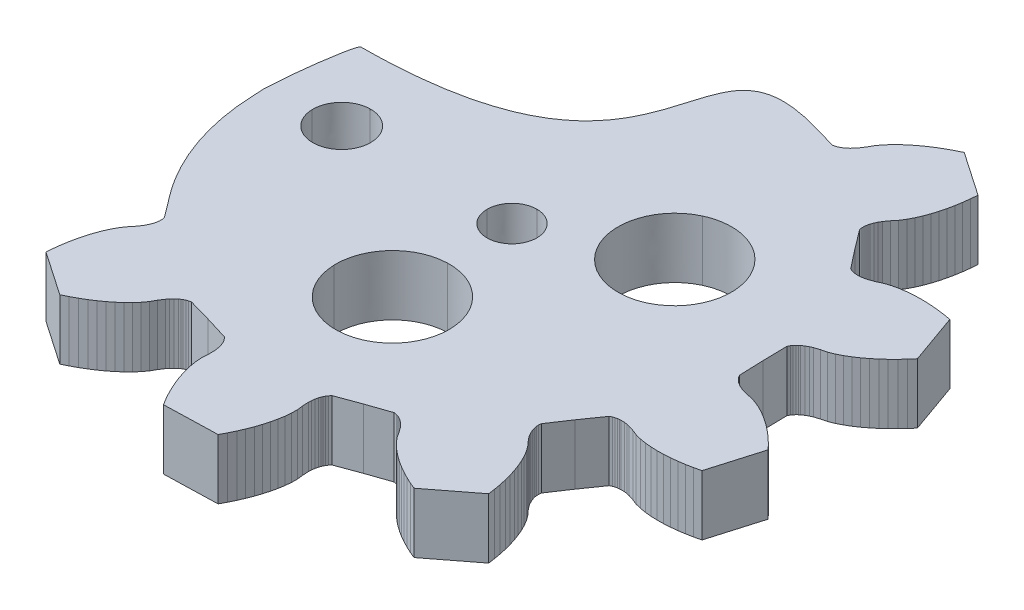
SolidWorks part; units mm, degrees
material "Acrylic (Medium-high impact)"
ref_plane "Front Plane" through (0, 0, 0) normal (0, 0, 1) x (1, 0, 0)
ref_plane "Top Plane" through (0, 0, 0) normal (0, 1, 0) x (1, 0, 0)
ref_plane "Right Plane" through (0, 0, 0) normal (1, 0, 0) x (0, 0, -1)
sketch "Sketch1" plane through (0, 0, 0) normal (0, 1, 0) x (1, 0, 0)
  line L0 (10.7037, 1.5046) -> (10.6812, 2.7875)
  line L1 (10.6812, 2.7875) -> (10.7422, 2.9087)
  line L2 (10.7422, 2.9087) -> (10.8065, 2.9999)
  line L3 (10.8065, 2.9999) -> (10.873, 3.0751)
  line L4 (10.873, 3.0751) -> (10.9407, 3.1393)
  line L5 (10.9407, 3.1393) -> (11.0092, 3.1955)
  line L6 (11.0092, 3.1955) -> (11.1488, 3.2908)
  line L7 (11.1488, 3.2908) -> (11.291, 3.3685)
  line L8 (11.291, 3.3685) -> (11.4351, 3.4325)
  line L9 (11.4351, 3.4325) -> (11.7287, 3.5294)
  line L10 (11.7287, 3.5294) -> (12.0254, 3.6057)
  line L11 (12.0254, 3.6057) -> (12.3155, 3.7204)
  line L12 (12.3155, 3.7204) -> (12.6002, 3.8632)
  line L13 (12.6002, 3.8632) -> (12.8799, 4.0289)
  line L14 (12.8799, 4.0289) -> (13.155, 4.2143)
  line L15 (13.155, 4.2143) -> (13.4253, 4.4178)
  line L16 (13.4253, 4.4178) -> (13.6904, 4.6381)
  line L17 (13.6904, 4.6381) -> (13.9504, 4.8747)
  line L18 (13.9504, 4.8747) -> (14.2047, 5.1263)
  line L19 (14.2047, 5.1263) -> (14.4534, 5.393)
  line L20 (14.4534, 5.393) -> (14.6958, 5.674)
  line L21 (14.6958, 5.674) -> (13.7536, 8.3269)
  line L22 (13.7536, 8.3269) -> (13.3887, 8.3913)
  line L23 (13.3887, 8.3913) -> (13.0276, 8.4407)
  line L24 (13.0276, 8.4407) -> (12.6717, 8.4749)
  line L25 (12.6717, 8.4749) -> (12.3211, 8.4938)
  line L26 (12.3211, 8.4938) -> (11.9764, 8.4967)
  line L27 (11.9764, 8.4967) -> (11.6387, 8.4833)
  line L28 (11.6387, 8.4833) -> (11.3085, 8.453)
  line L29 (11.3085, 8.453) -> (10.9871, 8.4044)
  line L30 (10.9871, 8.4044) -> (10.6763, 8.3351)
  line L31 (10.6763, 8.3351) -> (10.3793, 8.2405)
  line L32 (10.3793, 8.2405) -> (10.101, 8.1117)
  line L33 (10.101, 8.1117) -> (9.8124, 8.0012)
  line L34 (9.8124, 8.0012) -> (9.6601, 7.9597)
  line L35 (9.6601, 7.9597) -> (9.5011, 7.9299)
  line L36 (9.5011, 7.9299) -> (9.3329, 7.9154)
  line L37 (9.3329, 7.9154) -> (9.2442, 7.9156)
  line L38 (9.2442, 7.9156) -> (9.1513, 7.9227)
  line L39 (9.1513, 7.9227) -> (9.0525, 7.939)
  line L40 (9.0525, 7.939) -> (8.945, 7.9688)
  line L41 (8.945, 7.9688) -> (8.8213, 8.0241)
  line L42 (8.8213, 8.0241) -> (8.0297, 9.0328)
  line L43 (8.0297, 9.0328) -> (7.2586, 10.0578)
  line L44 (7.2586, 10.0578) -> (7.237, 10.192)
  line L45 (7.237, 10.192) -> (7.2356, 10.3036)
  line L46 (7.2356, 10.3036) -> (7.2453, 10.4034)
  line L47 (7.2453, 10.4034) -> (7.2622, 10.495)
  line L48 (7.2622, 10.495) -> (7.2848, 10.5812)
  line L49 (7.2848, 10.5812) -> (7.3417, 10.7403)
  line L50 (7.3417, 10.7403) -> (7.4112, 10.8869)
  line L51 (7.4112, 10.8869) -> (7.4902, 11.0235)
  line L52 (7.4902, 11.0235) -> (7.671, 11.2748)
  line L53 (7.671, 11.2748) -> (7.8661, 11.5114)
  line L54 (7.8661, 11.5114) -> (8.0336, 11.775)
  line L55 (8.0336, 11.775) -> (8.18, 12.0582)
  line L56 (8.18, 12.0582) -> (8.3091, 12.3569)
  line L57 (8.3091, 12.3569) -> (8.4229, 12.6689)
  line L58 (8.4229, 12.6689) -> (8.5221, 12.9925)
  line L59 (8.5221, 12.9925) -> (8.6074, 13.3271)
  line L60 (8.6074, 13.3271) -> (8.6791, 13.6714)
  line L61 (8.6791, 13.6714) -> (8.7371, 14.0249)
  line L62 (8.7371, 14.0249) -> (8.7818, 14.387)
  line L63 (8.7818, 14.387) -> (8.813, 14.7572)
  line L64 (8.813, 14.7572) -> (6.4943, 16.3485)
  line L65 (6.4943, 16.3485) -> (6.1611, 16.1857)
  line L66 (6.1611, 16.1857) -> (5.8402, 16.013)
  line L67 (5.8402, 16.013) -> (5.5321, 15.8312)
  line L68 (5.5321, 15.8312) -> (5.2374, 15.6398)
  line L69 (5.2374, 15.6398) -> (4.957, 15.4395)
  line L70 (4.957, 15.4395) -> (4.6913, 15.2298)
  line L71 (4.6913, 15.2298) -> (4.4421, 15.0108)
  line L72 (4.4421, 15.0108) -> (4.2108, 14.7822)
  line L73 (4.2108, 14.7822) -> (4, 14.5431)
  line L74 (4, 14.5431) -> (3.8149, 14.2916)
  line L75 (3.8149, 14.2916) -> (3.6655, 14.0236)
  line L76 (3.6655, 14.0236) -> (3.4969, 13.7644)
  line L77 (3.4969, 13.7644) -> (3.3982, 13.641)
  line L78 (3.3982, 13.641) -> (3.287, 13.5232)
  line L79 (3.287, 13.5232) -> (3.1591, 13.4124)
  line L80 (3.1591, 13.4124) -> (3.0873, 13.3603)
  line L81 (3.0873, 13.3603) -> (3.0081, 13.3113)
  line L82 (3.0081, 13.3113) -> (2.9187, 13.2664)
  line L83 (2.9187, 13.2664) -> (2.8143, 13.2271)
  line L84 (2.8143, 13.2271) -> (2.6818, 13.199)
  line L85 (2.6818, 13.199) -> (1.4492, 13.5492)
  line L86 (-14.9201, 0.7879) -> (-14.8842, 0.1165)
  line L87 (-12.425, -6.74) -> (-11.6539, -7.7649)
  line L88 (-11.6539, -7.7649) -> (-11.6324, -7.8989)
  line L89 (-11.6324, -7.8989) -> (-11.6311, -8.0107)
  line L90 (-11.6311, -8.0107) -> (-11.6405, -8.1103)
  line L91 (-11.6405, -8.1103) -> (-11.6577, -8.2021)
  line L92 (-11.6577, -8.2021) -> (-11.6802, -8.2883)
  line L93 (-11.6802, -8.2883) -> (-11.737, -8.4474)
  line L94 (-11.737, -8.4474) -> (-11.8067, -8.594)
  line L95 (-11.8067, -8.594) -> (-11.8857, -8.7307)
  line L96 (-11.8857, -8.7307) -> (-12.0661, -8.9818)
  line L97 (-12.0661, -8.9818) -> (-12.2615, -9.2185)
  line L98 (-12.2615, -9.2185) -> (-12.4288, -9.4819)
  line L99 (-12.4288, -9.4819) -> (-12.5752, -9.7653)
  line L100 (-12.5752, -9.7653) -> (-12.7045, -10.0639)
  line L101 (-12.7045, -10.0639) -> (-12.8182, -10.3758)
  line L102 (-12.8182, -10.3758) -> (-12.9174, -10.6997)
  line L103 (-12.9174, -10.6997) -> (-13.0027, -11.034)
  line L104 (-13.0027, -11.034) -> (-13.0743, -11.3784)
  line L105 (-13.0743, -11.3784) -> (-13.1324, -11.732)
  line L106 (-13.1324, -11.732) -> (-13.1769, -12.0941)
  line L107 (-13.1769, -12.0941) -> (-13.2085, -12.4643)
  line L108 (-13.2085, -12.4643) -> (-10.8897, -14.0555)
  line L109 (-10.8897, -14.0555) -> (-10.5564, -13.8926)
  line L110 (-10.5564, -13.8926) -> (-10.2355, -13.7201)
  line L111 (-10.2355, -13.7201) -> (-9.9274, -13.5381)
  line L112 (-9.9274, -13.5381) -> (-9.6328, -13.3471)
  line L113 (-9.6328, -13.3471) -> (-9.3521, -13.1466)
  line L114 (-9.3521, -13.1466) -> (-9.0868, -12.9369)
  line L115 (-9.0868, -12.9369) -> (-8.8374, -12.7179)
  line L116 (-8.8374, -12.7179) -> (-8.6062, -12.4893)
  line L117 (-8.6062, -12.4893) -> (-8.3951, -12.2504)
  line L118 (-8.3951, -12.2504) -> (-8.2104, -11.9985)
  line L119 (-8.2104, -11.9985) -> (-8.0607, -11.7307)
  line L120 (-8.0607, -11.7307) -> (-7.8923, -11.4715)
  line L121 (-7.8923, -11.4715) -> (-7.7936, -11.3481)
  line L122 (-7.7936, -11.3481) -> (-7.6821, -11.2303)
  line L123 (-7.6821, -11.2303) -> (-7.5547, -11.1195)
  line L124 (-7.5547, -11.1195) -> (-7.4826, -11.0674)
  line L125 (-7.4826, -11.0674) -> (-7.4033, -11.0184)
  line L126 (-7.4033, -11.0184) -> (-7.314, -10.9734)
  line L127 (-7.314, -10.9734) -> (-7.2095, -10.9344)
  line L128 (-7.2095, -10.9344) -> (-7.0771, -10.9061)
  line L129 (-7.0771, -10.9061) -> (-5.8445, -11.2561)
  line L130 (-5.8445, -11.2561) -> (-4.6194, -11.6315)
  line L131 (-4.6194, -11.6315) -> (-4.5234, -11.7269)
  line L132 (-4.5234, -11.7269) -> (-4.4566, -11.8165)
  line L133 (-4.4566, -11.8165) -> (-4.4059, -11.9029)
  line L134 (-4.4059, -11.9029) -> (-4.3658, -11.9872)
  line L135 (-4.3658, -11.9872) -> (-4.3334, -12.0702)
  line L136 (-4.3334, -12.0702) -> (-4.2863, -12.2324)
  line L137 (-4.2863, -12.2324) -> (-4.2566, -12.392)
  line L138 (-4.2566, -12.392) -> (-4.2403, -12.5491)
  line L139 (-4.2403, -12.5491) -> (-4.239, -12.8585)
  line L140 (-4.239, -12.8585) -> (-4.2583, -13.1649)
  line L141 (-4.2583, -13.1649) -> (-4.239, -13.4766)
  line L142 (-4.239, -13.4766) -> (-4.1913, -13.7921)
  line L143 (-4.1913, -13.7921) -> (-4.1206, -14.1098)
  line L144 (-4.1206, -14.1098) -> (-4.0295, -14.4291)
  line L145 (-4.0295, -14.4291) -> (-3.9199, -14.7495)
  line L146 (-3.9199, -14.7495) -> (-3.7927, -15.0704)
  line L147 (-3.7927, -15.0704) -> (-3.6485, -15.3912)
  line L148 (-3.6485, -15.3912) -> (-3.488, -15.7115)
  line L149 (-3.488, -15.7115) -> (-3.3116, -16.0306)
  line L150 (-3.3116, -16.0306) -> (-3.1198, -16.3485)
  line L151 (-3.1198, -16.3485) -> (-0.3102, -16.2705)
  line L152 (-0.3102, -16.2705) -> (-0.1364, -15.9426)
  line L153 (-0.1364, -15.9426) -> (0.0221, -15.614)
  line L154 (0.0221, -15.614) -> (0.1646, -15.2853)
  line L155 (0.1646, -15.2853) -> (0.2909, -14.9571)
  line L156 (0.2909, -14.9571) -> (0.4002, -14.6298)
  line L157 (0.4002, -14.6298) -> (0.492, -14.3037)
  line L158 (0.492, -14.3037) -> (0.5651, -13.9799)
  line L159 (0.5651, -13.9799) -> (0.6183, -13.6586)
  line L160 (0.6183, -13.6586) -> (0.6485, -13.3411)
  line L161 (0.6485, -13.3411) -> (0.6505, -13.0286)
  line L162 (0.6505, -13.0286) -> (0.6143, -12.7239)
  line L163 (0.6143, -12.7239) -> (0.5985, -12.4149)
  line L164 (0.5985, -12.4149) -> (0.6061, -12.2569)
  line L165 (0.6061, -12.2569) -> (0.627, -12.0961)
  line L166 (0.627, -12.0961) -> (0.665, -11.9312)
  line L167 (0.665, -11.9312) -> (0.6929, -11.8468)
  line L168 (0.6929, -11.8468) -> (0.7282, -11.7605)
  line L169 (0.7282, -11.7605) -> (0.774, -11.6714)
  line L170 (0.774, -11.6714) -> (0.8356, -11.5783)
  line L171 (0.8356, -11.5783) -> (0.9264, -11.4774)
  line L172 (0.9264, -11.4774) -> (2.1289, -11.0351)
  line L173 (2.1289, -11.0351) -> (3.3401, -10.6171)
  line L174 (3.3401, -10.6171) -> (3.4739, -10.638)
  line L175 (3.4739, -10.638) -> (3.5804, -10.671)
  line L176 (3.5804, -10.671) -> (3.6722, -10.7111)
  line L177 (3.6722, -10.7111) -> (3.7541, -10.7557)
  line L178 (3.7541, -10.7557) -> (3.8289, -10.8036)
  line L179 (3.8289, -10.8036) -> (3.9623, -10.9072)
  line L180 (3.9623, -10.9072) -> (4.0798, -11.0188)
  line L181 (4.0798, -11.0188) -> (4.1853, -11.1364)
  line L182 (4.1853, -11.1364) -> (4.368, -11.3858)
  line L183 (4.368, -11.3858) -> (4.532, -11.6449)
  line L184 (4.532, -11.6449) -> (4.7305, -11.886)
  line L185 (4.7305, -11.886) -> (4.9542, -12.113)
  line L186 (4.9542, -12.113) -> (5.198, -12.3284)
  line L187 (5.198, -12.3284) -> (5.4589, -12.5332)
  line L188 (5.4589, -12.5332) -> (5.7357, -12.7278)
  line L189 (5.7357, -12.7278) -> (6.0269, -12.9124)
  line L190 (6.0269, -12.9124) -> (6.3317, -13.0871)
  line L191 (6.3317, -13.0871) -> (6.6493, -13.2516)
  line L192 (6.6493, -13.2516) -> (6.9791, -13.4062)
  line L193 (6.9791, -13.4062) -> (7.3208, -13.5503)
  line L194 (7.3208, -13.5503) -> (9.5481, -11.8329)
  line L195 (9.5481, -11.8329) -> (9.4964, -11.4649)
  line L196 (9.4964, -11.4649) -> (9.4318, -11.1059)
  line L197 (9.4318, -11.1059) -> (9.3544, -10.756)
  line L198 (9.3544, -10.756) -> (9.2639, -10.4162)
  line L199 (9.2639, -10.4162) -> (9.1601, -10.0869)
  line L200 (9.1601, -10.0869) -> (9.0432, -9.7693)
  line L201 (9.0432, -9.7693) -> (8.9124, -9.4639)
  line L202 (8.9124, -9.4639) -> (8.767, -9.1731)
  line L203 (8.767, -9.1731) -> (8.6051, -8.8982)
  line L204 (8.6051, -8.8982) -> (8.4234, -8.6444)
  line L205 (8.4234, -8.6444) -> (8.2153, -8.419)
  line L206 (8.2153, -8.419) -> (8.021, -8.1783)
  line L207 (8.021, -8.1783) -> (7.9346, -8.0462)
  line L208 (7.9346, -8.0462) -> (7.8573, -7.9038)
  line L209 (7.8573, -7.9038) -> (7.7914, -7.748)
  line L210 (7.7914, -7.748) -> (7.7642, -7.6632)
  line L211 (7.7642, -7.6632) -> (7.7423, -7.5727)
  line L212 (7.7423, -7.5727) -> (7.727, -7.4734)
  line L213 (7.727, -7.4734) -> (7.7222, -7.3621)
  line L214 (7.7222, -7.3621) -> (7.7365, -7.2271)
  line L215 (7.7365, -7.2271) -> (8.4497, -6.1608)
  line L216 (8.4497, -6.1608) -> (9.1844, -5.1096)
  line L217 (9.1844, -5.1096) -> (9.305, -5.0475)
  line L218 (9.305, -5.0475) -> (9.4104, -5.0118)
  line L219 (9.4104, -5.0118) -> (9.5082, -4.9901)
  line L220 (9.5082, -4.9901) -> (9.6006, -4.9779)
  line L221 (9.6006, -4.9779) -> (9.6891, -4.9728)
  line L222 (9.6891, -4.9728) -> (9.8579, -4.9779)
  line L223 (9.8579, -4.9779) -> (10.0185, -4.9988)
  line L224 (10.0185, -4.9988) -> (10.1728, -5.0319)
  line L225 (10.1728, -5.0319) -> (10.467, -5.1263)
  line L226 (10.467, -5.1263) -> (10.752, -5.2392)
  line L227 (10.752, -5.2392) -> (11.0539, -5.3173)
  line L228 (11.0539, -5.3173) -> (11.3681, -5.369)
  line L229 (11.3681, -5.369) -> (11.6916, -5.4001)
  line L230 (11.6916, -5.4001) -> (12.0228, -5.4121)
  line L231 (12.0228, -5.4121) -> (12.3608, -5.4066)
  line L232 (12.3608, -5.4066) -> (12.7047, -5.3845)
  line L233 (12.7047, -5.3845) -> (13.0538, -5.3462)
  line L234 (13.0538, -5.3462) -> (13.4075, -5.2923)
  line L235 (13.4075, -5.2923) -> (13.765, -5.223)
  line L236 (13.765, -5.223) -> (14.1259, -5.1384)
  line L237 (14.1259, -5.1384) -> (14.9201, -2.4373)
  line L238 (14.9201, -2.4373) -> (14.6625, -2.1704)
  line L239 (14.6625, -2.1704) -> (14.3996, -1.9179)
  line L240 (14.3996, -1.9179) -> (14.1318, -1.6804)
  line L241 (14.1318, -1.6804) -> (13.859, -1.4589)
  line L242 (13.859, -1.4589) -> (13.5819, -1.2535)
  line L243 (13.5819, -1.2535) -> (13.3008, -1.0654)
  line L244 (13.3008, -1.0654) -> (13.0159, -0.8955)
  line L245 (13.0159, -0.8955) -> (12.7277, -0.7457)
  line L246 (12.7277, -0.7457) -> (12.4353, -0.6187)
  line L247 (12.4353, -0.6187) -> (12.1395, -0.5203)
  line L248 (12.1395, -0.5203) -> (11.839, -0.4605)
  line L249 (11.839, -0.4605) -> (11.5407, -0.3801)
  line L250 (11.5407, -0.3801) -> (11.3931, -0.3242)
  line L251 (11.3931, -0.3242) -> (11.2468, -0.2544)
  line L252 (11.2468, -0.2544) -> (11.1023, -0.1671)
  line L253 (11.1023, -0.1671) -> (11.0305, -0.1147)
  line L254 (11.0305, -0.1147) -> (10.9596, -0.0542)
  line L255 (10.9596, -0.0542) -> (10.8891, 0.0171)
  line L256 (10.8891, 0.0171) -> (10.8198, 0.1045)
  line L257 (10.8198, 0.1045) -> (10.752, 0.2219)
  line L258 (10.752, 0.2219) -> (10.7037, 1.5046)
  spline S0 degree 3 poles (1.4492, 13.5492) (-6.9443, 15.9791) (2.0968, 5.2988) (-14.2763, 5.233) knots 86 86 86 86 87 87 87 87
  spline S1 degree 3 poles (-14.2763, 5.233) (-14.4534, 5.2143) (-14.8524, 2.5186) (-14.9201, 0.7879) knots 87 87 87 87 88 88 88 88
  spline S2 degree 3 poles (-14.8842, 0.1165) (-14.7409, -3.4334) (-13.1804, -5.776) (-12.425, -6.74) knots 89 89 89 89 90 90 90 90
  spline S3 degree 3 poles (-2.1977, 2.4623) (-2.923, 2.4623) (-3.511, 1.8731) (-3.511, 1.1465) knots 3 3 3 3 4 4 4 4
  spline S4 degree 3 poles (-2.1977, -0.1693) (-1.4723, -0.1695) (-0.8841, 0.4198) (-0.8841, 1.1465) (-0.8841, 1.8731) (-1.4723, 2.4622) (-2.1977, 2.4623) knots 1 1 1 1 2 2 2 3 3 3 3
  spline S5 degree 3 poles (-3.511, 1.1465) (-3.511, 0.4198) (-2.923, -0.1693) (-2.1977, -0.1693) knots 0 0 0 0 1 1 1 1
  spline S6 degree 3 poles (-12.6925, 1.0855) (-12.7093, 1.9302) (-12.0391, 2.6289) (-11.1959, 2.6456) knots 3 3 3 3 4 4 4 4
  spline S7 degree 3 poles (-11.1351, -0.4138) (-11.9785, -0.4305) (-12.6757, 0.2406) (-12.6925, 1.0855) knots 2 2 2 2 3 3 3 3
  spline S8 degree 3 poles (-9.6386, 1.1465) (-9.6217, 0.3016) (-10.2919, -0.397) (-11.1351, -0.4138) knots 1 1 1 1 2 2 2 2
  spline S9 degree 3 poles (-11.1959, 2.6456) (-10.3525, 2.6625) (-9.6555, 1.991) (-9.6386, 1.1465) knots 0 0 0 0 1 1 1 1
  spline S10 degree 3 poles (0.9879, -5.2623) (1.0437, -6.9181) (-0.2512, -8.3059) (-1.9041, -8.3618) knots 3 3 3 3 4 4 4 4
  spline S11 degree 3 poles (-2.1059, -2.3651) (-0.4529, -2.3092) (0.9321, -3.6065) (0.9879, -5.2623) knots 2 2 2 2 3 3 3 3
  spline S12 degree 3 poles (-4.9977, -5.4645) (-5.0534, -3.8086) (-3.7588, -2.421) (-2.1059, -2.3651) knots 1 1 1 1 2 2 2 2
  spline S13 degree 3 poles (-1.9041, -8.3618) (-3.557, -8.4176) (-4.9421, -7.1204) (-4.9977, -5.4645) knots 0 0 0 0 1 1 1 1
  spline S14 degree 3 poles (2.4793, 6.5222) (3.9777, 7.2222) (5.7592, 6.5728) (6.4581, 5.0715) knots 3 3 3 3 4 4 4 4
  spline S15 degree 3 poles (5.0098, 1.0857) (3.5114, 0.3857) (1.7301, 1.035) (1.0312, 2.5364) (0.3323, 4.0377) (0.9807, 5.8223) (2.4793, 6.5222) knots 1 1 1 1 2 2 2 3 3 3 3
  spline S16 degree 3 poles (6.4581, 5.0715) (7.1568, 3.5702) (6.5084, 1.7858) (5.0098, 1.0857) knots 0 0 0 0 1 1 1 1
extrude "Boss-Extrude1" add sketch "Sketch1" along normal blind 3.175
